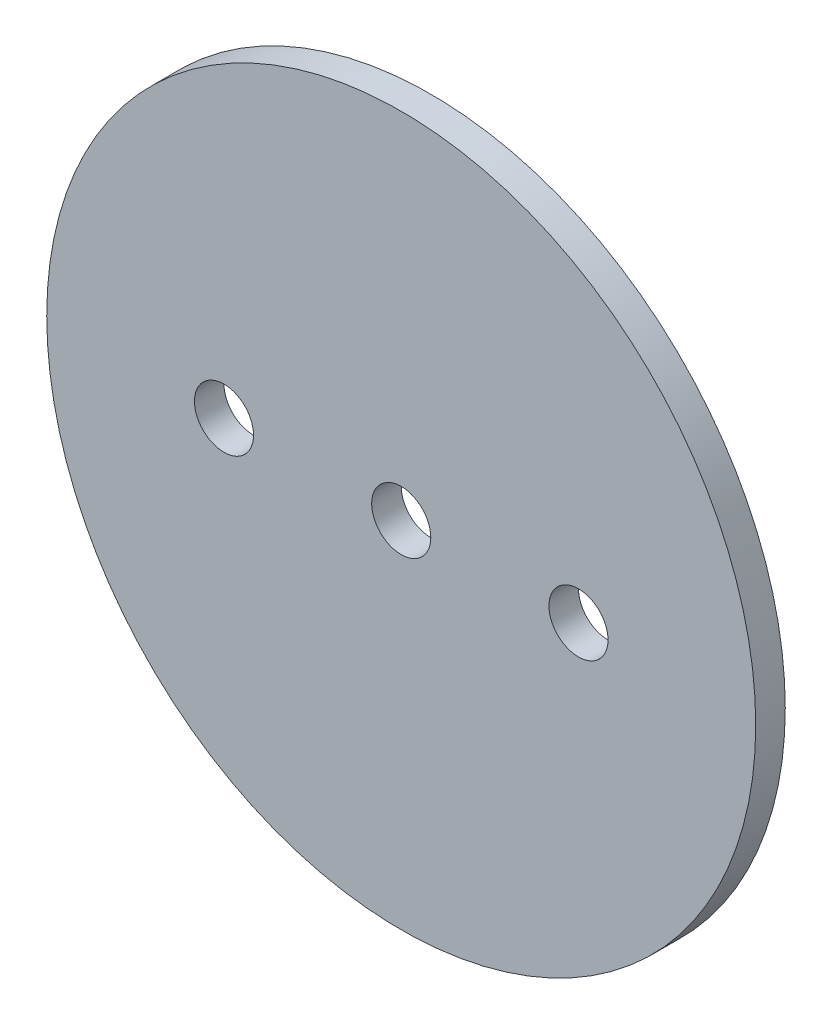
SolidWorks part; units mm, degrees
ref_plane "Front Plane" through (0, 0, 0) normal (0, 0, 1) x (1, 0, 0)
ref_plane "Top Plane" through (0, 0, 0) normal (0, 1, 0) x (1, 0, 0)
ref_plane "Right Plane" through (0, 0, 0) normal (1, 0, 0) x (0, 0, -1)
sketch "Sketch1" plane through (0, 0, 0) normal (0, 0, 1) x (1, 0, 0)
  circle A0 centre (0, 0) radius 38.1
extrude "Boss-Extrude1" add sketch "Sketch1" along normal mid plane 3.175
sketch "Sketch2" plane through (0, 0, 1.5875) normal (0, 0, 1) x (1, 0, 0)
  line L0 (-1000, 0) -> (49000, 0) construction
  point P1 (0, 0)
  point P4 (19.05, 0)
  point P5 (-19.05, 0)
  dimension "D1" = 19.05
  dimension "D2" = 38.1
hole_wizard "1/4 (0.25) Diameter Hole1" positions "Sketch2" profile "Sketch3" hole size "1/4" standard "ANSI Inch" end condition through all
sketch "Sketch3" plane through (-19.05, 0, 1.5875) normal (1, 0, 0) x (0, -1, 0)
  line L0 (0, 0) -> (0, 3.175)
  line L1 (0, 3.175) -> (3.175, 3.175)
  line L2 (3.175, 3.175) -> (3.175, 0)
  line L5 (3.175, 0) -> (0, 0)
  line L11 (0, -6.35) -> (0, 107.95) construction
  dimension "Thru Hole Dia." = 6.35
  dimension "Thru Hole Depth" = 3.175
equation "\"AIRFRAME_OD\"= 3.091in"
equation "\"AIRFRAME_ID\"= 3.00in"
equation "\"FLAT_T\"= 0.125in"
equation "\"NOSE_EXP_L\"= 3.5in"
equation "\"NOSE_SHOULDER_L\"= 5in"
equation "\"MAIN_L\"= 30in"
equation "\"RECO_COUP_L\"= 6in"
equation "\"RECO_SWITCH_L\"= 1.5in"
equation "\"DROGUE_L\"= 14in"
equation "\"ATS_FORE_COUP_L\"= 4in"
equation "\"ATS_AFT_COUP_L\"= 2.5in"
equation "\"LOWER_L\"= 16in"
equation "\"FIN_N\"= 4"
equation "\"CR_AFT_X\"= 0.5in"
equation "\"CR_FORE_X\"= 6in"
equation "\"FIN_ROOT\"= 5in"
equation "\"FIN_X\"= 0.75in"
equation "\"MOTOR_OD\"= 2.25in"
equation "\"MOTOR_ID\"= 2.126in"
equation "\"COUPLER_OD\"= 2.998in"
equation "\"COUPLER_ID\"= 2.875in"
equation "\"D1@Sketch1\"=\"AIRFRAME_ID\""
equation "\"D1@Boss-Extrude1\"=\"FLAT_T\""
equation "\"RECO_ROD_X\"= 1.5in"
equation "\"ATS_ROD_X\"= 2in"
equation "\"D1@Sketch2\"=\"RECO_ROD_X\"*0.5"
equation "\"D2@Sketch2\"=\"RECO_ROD_X\""
